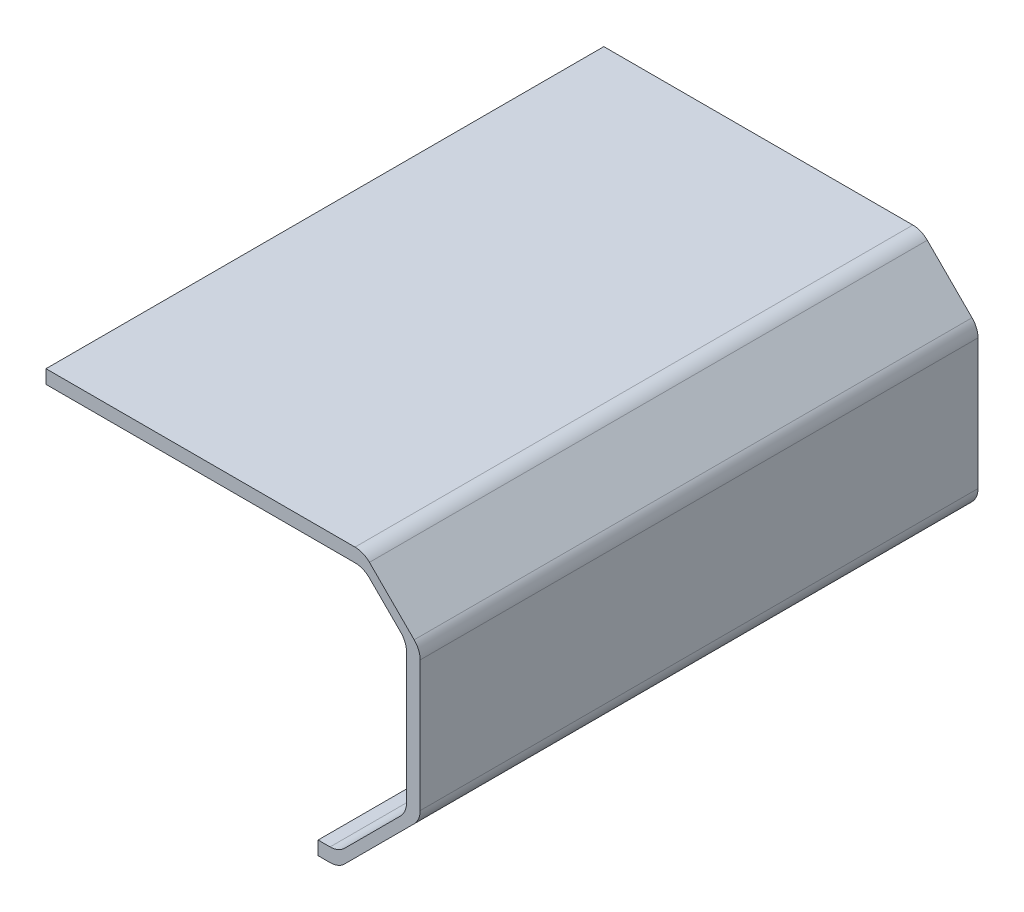
SolidWorks part; units mm, degrees
ref_plane "前视基准面" through (0, 0, 0) normal (0, 0, 1) x (1, 0, 0)
ref_plane "上视基准面" through (0, 0, 0) normal (0, 1, 0) x (1, 0, 0)
ref_plane "右视基准面" through (0, 0, 0) normal (1, 0, 0) x (0, 0, -1)
sketch "草图1" plane through (0, 0, 0) normal (0, 0, 1) x (1, 0, 0)
  line L1 (0, 2) -> (3, 2)
  line L7 (0, 0) -> (3, 0)
  line L14 (-40, 42) -> (-40, 40)
  line L15 (3, 2) -> (13, 12)
  line L16 (3, 0) -> (15, 12)
  line L18 (15, 12) -> (15, 33.6667)
  line L21 (13, 12) -> (13, 33.6667)
  line L22 (13, 33.6667) -> (6.6667, 40)
  line L23 (-40, 40) -> (6.6667, 40)
  line L24 (15, 33.6667) -> (6.6667, 42)
  line L25 (-40, 42) -> (6.6667, 42)
  line L26 (0, 0) -> (0, 2)
  point P5 (0, 0)
extrude "凸台-拉伸1" add sketch "草图1" along normal blind 82
fillet "圆角1" radius 3 8 edges at (3, 0, 41) (15, 12, 41) (3, 2, 41) (6.6667, 42, 41) (15, 33.6667, 41) (6.6667, 40, 41) (13, 33.6667, 41) (13, 12, 41)
